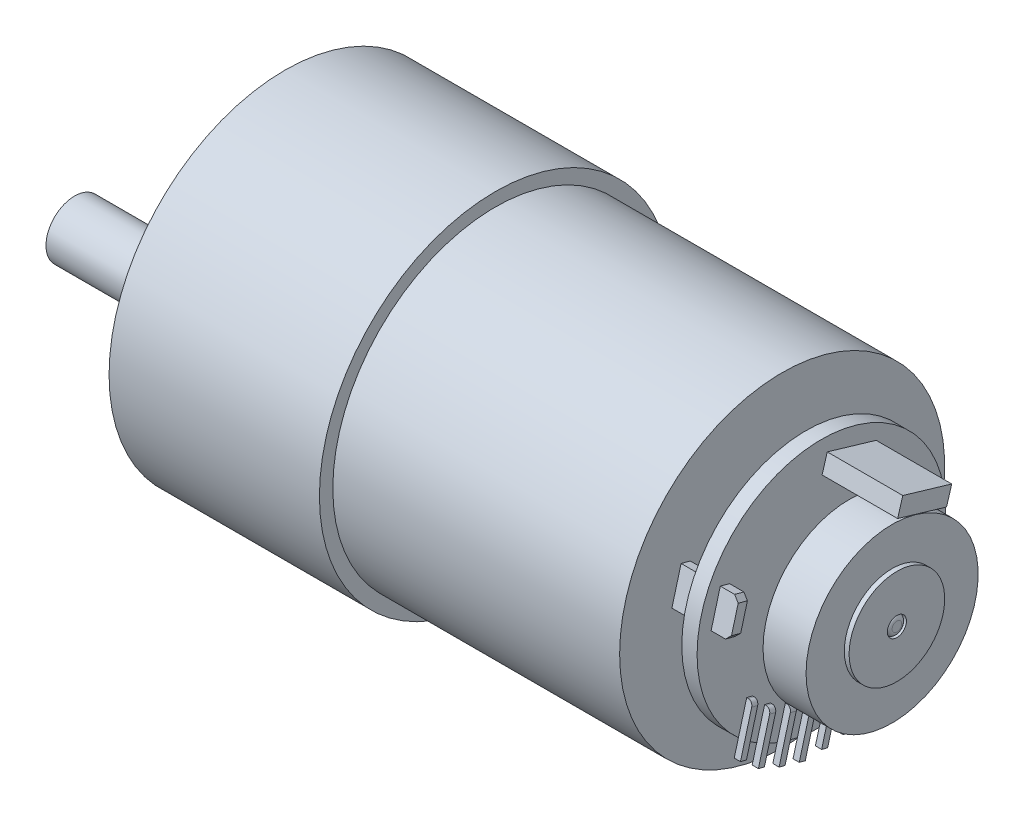
SolidWorks part; units mm, degrees
material "Pololu 37D"
ref_plane "Front Plane" through (0, 0, 0) normal (0, 0, 1) x (1, 0, 0)
ref_plane "Top Plane" through (0, 0, 0) normal (0, 1, 0) x (1, 0, 0)
ref_plane "Right Plane" through (0, 0, 0) normal (1, 0, 0) x (0, 0, -1)
sketch "Sketch1" plane through (0, 0, 0) normal (0, 0, 1) x (1, 0, 0)
  line L0 (0, 0) -> (64, 0)
  line L1 (52, 1) -> (54.5, 1)
  line L2 (54.5, 1) -> (54.5, 13)
  line L3 (52, 1) -> (52, 17)
  line L4 (52, 17) -> (22, 17)
  line L5 (22, 17) -> (22, 18.4)
  line L6 (22, 18.4) -> (0, 18.4)
  line L7 (0, 18.4) -> (0, 0)
  line L8 (54.5, 13) -> (56.1, 13)
  line L9 (56.1, 13) -> (56.1, 1)
  line L10 (56.1, 1) -> (59, 1)
  line L11 (59, 1) -> (59, 9)
  line L12 (59, 9) -> (63.5, 9)
  line L13 (63.5, 9) -> (63.5, 5)
  line L14 (63.5, 5) -> (64, 5)
  line L15 (64, 5) -> (64, 1)
  line L16 (64, 1) -> (63.5, 1)
  line L17 (64, 0.5) -> (64, 0)
  arc A0 (63.5, 1) -> (64, 0.5) centre (63.5, 0.5) cw
  dimension "D1" = 22
  dimension "D2" = 30
  dimension "D3" = 5
  dimension "D4" = 18.4
  dimension "D5" = 17
  dimension "D6" = 13
  dimension "D7" = 1
  dimension "D8" = 1.6
  dimension "D9" = 2.5
  dimension "D10" = 12
  dimension "D11" = 9
  dimension "D12" = 0.5
  dimension "D13" = 1
  dimension "D14" = 7
revolve "Revolve1" add sketch "Sketch1" angle 360 about L0
sketch "Sketch2" plane through (0, 0, 0) normal (-1, 0, 0) x (0, 0, 1)
  circle A0 centre (0, -7) radius 6
  dimension "D2" = 12
  dimension "D1" = 7
extrude "Boss-Extrude1" add sketch "Sketch2" along normal blind 6.5
sketch "Sketch3" plane through (-6.5, 0, 0) normal (-1, 0, 0) x (0, 0, 1)
  circle A0 centre (0, -7) radius 3
  dimension "D1" = 6
extrude "Boss-Extrude2" add sketch "Sketch3" along normal blind 15.5
sketch "Sketch4" plane through (-22, 0, 0) normal (-1, 0, 0) x (0, 0, 1)
  line L0 (1.5, -9.5981) -> (-1.5, -9.5981)
  circle A0 centre (0, -7) radius 3 construction
  arc A1 (-1.5, -9.5981) -> (1.5, -9.5981) centre (0, -7) ccw
  dimension "D1" = 3
extrude "Cut-Extrude1" cut sketch "Sketch4" against normal blind 12
chamfer "Chamfer1" distance 1 angle 45 1 edges at (-6.5, -7, 6)
sketch "Sketch5" plane through (0, 0, 0) normal (-1, 0, 0) x (0, 0, 1)
  circle A0 centre (15.5, 0) radius 1.23
  dimension "D1" = 2.46
  dimension "D2" = 15.5
extrude "Cut-Extrude2" cut sketch "Sketch5" against normal blind 5
pattern_circular "CirPattern1" count 6 over 360 about axis through (0, 0, 0) along (-1, 0, 0) of "Cut-Extrude2"
sketch "Sketch6" plane through (56.1, 0, 0) normal (1, 0, 0) x (0, 0, -1)
  line L0 (0.6145, 11.5591) -> (5.7344, 10.0452)
  line L1 (0.6145, 11.5591) -> (0.0765, 9.7397)
  line L2 (5.7344, 10.0452) -> (5.1964, 8.2257)
  line L3 (0.0765, 9.7397) -> (5.1964, 8.2257)
extrude "Boss-Extrude3" add sketch "Sketch6" along normal up to surface (7.9 mm away) up to face at (64, 0, 5)
sketch "Sketch7" plane through (52, 0, 0) normal (1, 0, 0) x (0, 0, -1)
  line L0 (-10.5696, 4.9937) -> (-11.5324, 1.4314)
  line L1 (-10.5696, 4.9937) -> (-9.6043, 4.7328)
  line L2 (-11.5324, 1.4314) -> (-10.5671, 1.1705)
  line L3 (-9.6043, 4.7328) -> (-10.5671, 1.1705)
  line L4 (10.9602, -0.8251) -> (9.9974, -4.3875)
  line L5 (10.9602, -0.8251) -> (11.9256, -1.086)
  line L6 (9.9974, -4.3875) -> (10.9628, -4.6484)
  line L7 (11.9256, -1.086) -> (10.9628, -4.6484)
  dimension "D1" = 1
extrude "Boss-Extrude4" add sketch "Sketch7" along normal offset from surface (6.1 mm away) 2 up to face at (56.1, 0, 1) offset beyond the face yes
chamfer "Chamfer2" distance 0.5 angle 45 4 edges at (58.1, -4.518, -10.4801) (58.1, -0.9556, -11.4429) (58.1, 1.3009, 11.0498) (58.1, 4.8633, 10.087)
sketch "Sketch9" plane through (56.1, 0, 0) normal (1, 0, 0) x (0, 0, -1)
  line L0 (-7.8077, -6.481) -> (-9.1122, -11.3078)
  line L1 (-7.8077, -6.481) -> (-7.1802, -6.6506)
  line L2 (-9.1122, -11.3078) -> (-8.4848, -11.4774)
  line L3 (-7.1802, -6.6506) -> (-8.4848, -11.4774)
  line L4 (-10.5671, 1.1705) -> (-9.6043, 4.7328) construction
  line L5 (-5.9326, -8.0526) -> (-7.2372, -12.8794)
  line L6 (-5.9326, -8.0526) -> (-5.3051, -8.2222)
  line L7 (-7.2372, -12.8794) -> (-6.6097, -13.049)
  line L8 (-5.3051, -8.2222) -> (-6.6097, -13.049)
  line L9 (-3.7695, -8.9959) -> (-5.074, -13.8227)
  line L10 (-3.7695, -8.9959) -> (-3.142, -9.1655)
  line L11 (-5.074, -13.8227) -> (-4.4465, -13.9923)
  line L12 (-3.142, -9.1655) -> (-4.4465, -13.9923)
  line L13 (-1.6579, -9.6219) -> (-2.9624, -14.4487)
  line L14 (-1.6579, -9.6219) -> (-1.0304, -9.7915)
  line L15 (-2.9624, -14.4487) -> (-2.3349, -14.6183)
  line L16 (-1.0304, -9.7915) -> (-2.3349, -14.6183)
  line L17 (0.6801, -9.6246) -> (-0.6244, -14.4514)
  line L18 (0.6801, -9.6246) -> (1.3076, -9.7942)
  line L19 (-0.6244, -14.4514) -> (0.003, -14.621)
  line L20 (1.3076, -9.7942) -> (0.003, -14.621)
  line L21 (2.9201, -9.3953) -> (1.6156, -14.2221)
  line L22 (2.9201, -9.3953) -> (3.5476, -9.5648)
  line L23 (1.6156, -14.2221) -> (2.2431, -14.3917)
  line L24 (3.5476, -9.5648) -> (2.2431, -14.3917)
  dimension "D1" = 0.65
  dimension "D2" = 5
extrude "Boss-Extrude5" add sketch "Sketch9" along normal blind 0.65
fillet "Fillet1" radius 0.5 6 edges at (56.75, -9.48, -3.2339) (56.75, -9.7094, -0.9938) (56.75, -9.7067, 1.3441) (56.75, -9.0807, 3.4557) (56.75, -8.1374, 5.6189) (56.75, -6.5658, 7.494)
sketch "Sketch10" plane through (0, -12.8331, 3.4684) normal (0, -0.9654, 0.2609) x (1, 0, 0)
  line L0 (56.75, 5.1963) -> (56.1, 5.1963) construction
  line L1 (56.75, 5.8463) -> (56.1, 5.8463) construction
  line L3 (56.75, 5.8463) -> (56.75, 5.1963) construction
  line L4 (56.75, 3.6261) -> (56.75, 2.9761) construction
  line L5 (56.75, 2.9761) -> (56.1, 2.9761) construction
  line L6 (56.75, 3.6261) -> (56.1, 3.6261) construction
  circle A0 centre (56.425, 5.5213) radius 0.325
  circle A1 centre (56.425, 3.3011) radius 0.325
sketch "Sketch13" plane through (0, -12.847, 3.4722) normal (0, -0.9654, 0.2609) x (1, 0, 0)
  line L0 (56.75, -5.2703) -> (56.75, -5.9203) construction
  line L1 (56.75, -5.9203) -> (56.1, -5.9203) construction
  circle A0 centre (56.425, -5.5953) radius 0.325
  circle A1 centre (56.425, -3.4053) radius 0.325
  circle A2 centre (56.425, -1.2153) radius 0.325
  circle A3 centre (56.425, 0.9747) radius 0.325
  dimension "D1" = 0.65
  dimension "D2" = 4
sketch "Sketch14" plane through (0, 0, 0) normal (-1, 0, 0) x (0, 0, 1)
  arc A0 (-9.6139, -7.1815) -> (9.6139, -7.1815) centre (0, 0) cw
  arc A1 (-7.9936, -6.679) -> (7.9936, -6.679) centre (0, -7) cw
  arc A2 (-9.6139, -7.1815) -> (-7.9936, -6.679) centre (-8.8928, -6.6429) ccw
  arc A3 (7.9936, -6.679) -> (9.6139, -7.1815) centre (8.8928, -6.6429) ccw
  dimension "D1" = 12
  dimension "D2" = 8
  dimension "D3" = 0.9
extrude "Cut-Extrude3" cut sketch "Sketch14" against normal blind 1
